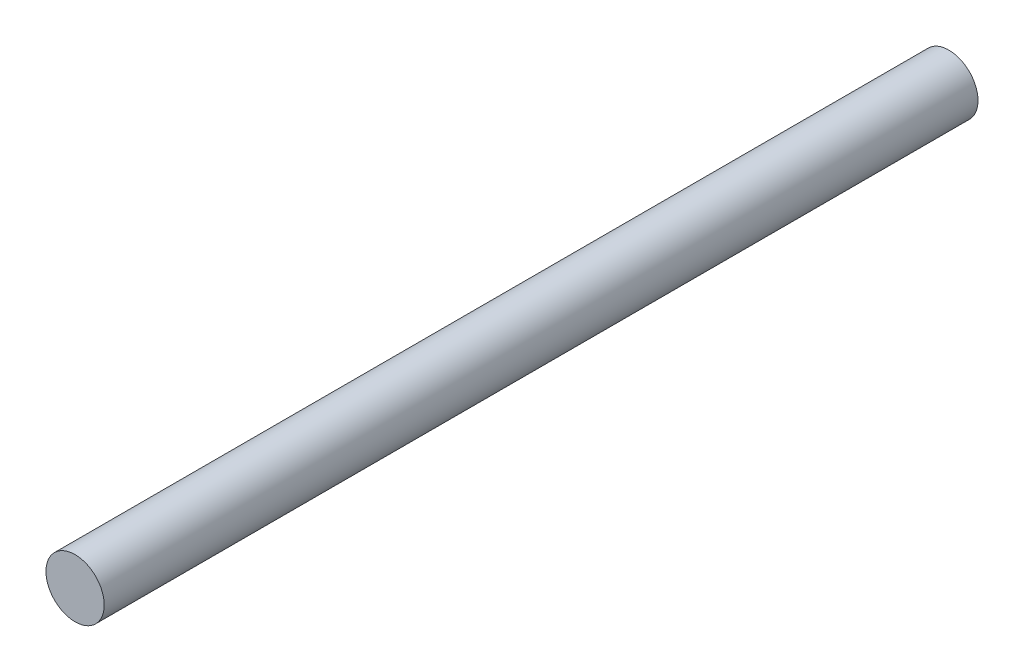
SolidWorks part; units mm, degrees
ref_plane "Front Plane" through (0, 0, 0) normal (0, 0, 1) x (1, 0, 0)
ref_plane "Top Plane" through (0, 0, 0) normal (0, 1, 0) x (1, 0, 0)
ref_plane "Right Plane" through (0, 0, 0) normal (1, 0, 0) x (0, 0, -1)
sketch "Sketch1" plane through (0, 0, 0) normal (0, 1, 0) x (1, 0, 0)
  line L0 (0, -48.7094) -> (0, -46.4499) construction
  line L1 (-4, 0) -> (0, 0)
  line L2 (-4, 0) -> (-4, -120)
  line L3 (-4, -120) -> (0, -120)
  line L4 (0, 0) -> (0, -120)
  dimension "D1" = 8
  dimension "D2" = 120
revolve "Revolve1" add sketch "Sketch1" angle 360 about L0
ref_axis "Axis1" through (0, 0, 63) along (0, 0, -1)
